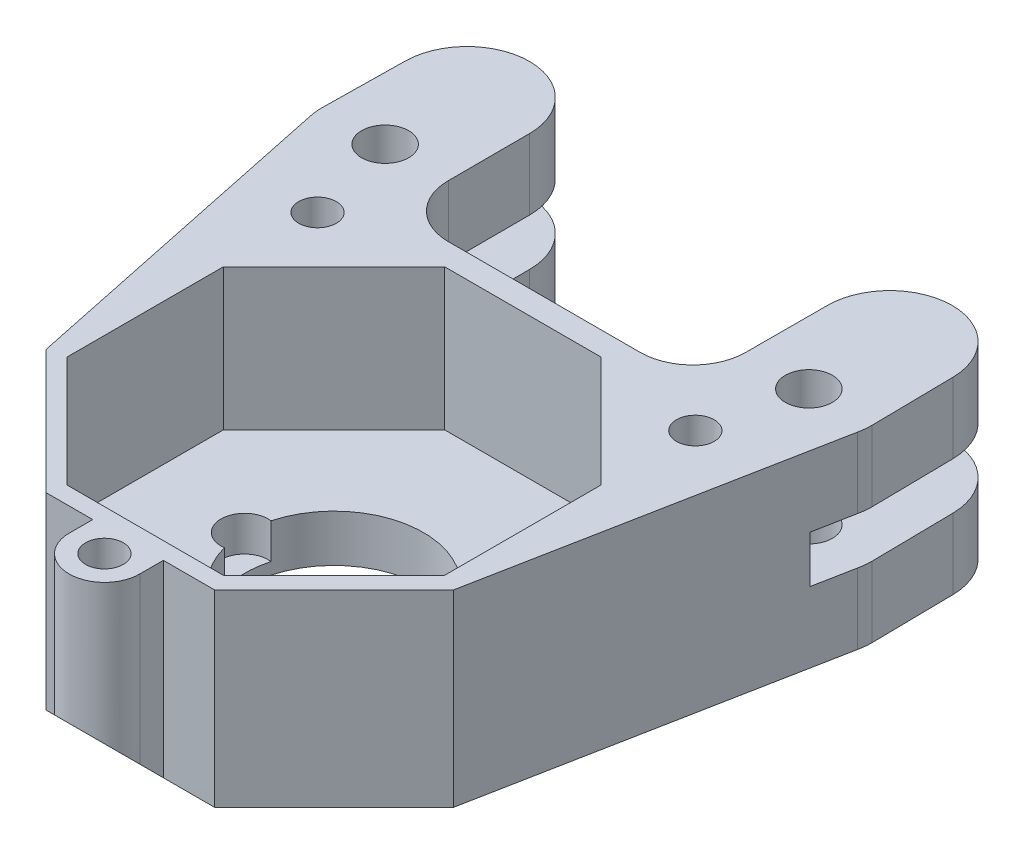
SolidWorks part; units mm, degrees
ref_plane "Front Plane" through (0, 0, 0) normal (0, 0, 1) x (1, 0, 0)
ref_plane "Top Plane" through (0, 0, 0) normal (0, 1, 0) x (1, 0, 0)
ref_plane "Right Plane" through (0, 0, 0) normal (1, 0, 0) x (0, 0, -1)
sketch "Sketch1" plane through (0, 0, 0) normal (0, 1, 0) x (1, 0, 0)
  line L0 (7.561, -35.5569) -> (17.6969, -25.421)
  line L1 (-6.7734, -35.5569) -> (7.561, -35.5569)
  line L3 (-7.1672, 0) -> (7.1672, 0)
  line L5 (-6.7734, -35.5569) -> (-17.3031, -25.0272)
  line L8 (-8.1516, 0) -> (8.1516, 0)
  line L10 (-17.3031, -25.0272) -> (-23.2516, 3.3834)
  line L12 (17.6969, -25.421) -> (23.2516, 3.3834)
  line L13 (-12.6345, 4.483) -> (-12.6501, 11.3996)
  line L14 (17.9118, 16.7228) -> (17.9119, 16.707)
  line L15 (-23.2647, 11.4761) -> (-23.3655, 4.483)
  line L16 (0, 0) -> (0, 17.0676)
  line L17 (23.2647, 11.4761) -> (23.3655, 4.483)
  line L20 (-17.9118, 16.7228) -> (-17.9119, 16.707)
  line L21 (23.2647, 11.4761) -> (23.3655, 4.483)
  line L22 (12.6345, 4.483) -> (12.6501, 11.3996)
  circle A0 centre (-18, 4.483) radius 2
  arc A1 (-23.3632, 4.6376) -> (-23.2516, 3.3834) centre (-18, 4.483) ccw
  arc A2 (23.3632, 4.6376) -> (23.2516, 3.3834) centre (18, 4.483) cw
  circle A3 centre (18, 4.483) radius 2
  arc A4 (-12.6345, 4.483) -> (-8.1516, 0) centre (-8.1516, 4.483) ccw
  arc A5 (12.6345, 4.483) -> (8.1516, 0) centre (8.1516, 4.483) cw
  arc A7 (-12.6501, 11.3996) -> (-23.2647, 11.4761) centre (-17.9577, 11.3996) ccw
  arc A8 (12.6501, 11.3996) -> (23.2647, 11.4761) centre (17.9577, 11.3996) cw
  arc A9 (12.6345, 4.483) -> (8.1516, 0) centre (8.1516, 4.483) cw
  arc A10 (23.3632, 4.6376) -> (23.2516, 3.3834) centre (18, 4.483) cw
  circle A11 centre (18, 4.483) radius 2
  circle A12 centre (0.1969, -18.0569) radius 7.6
extrude "Boss-Extrude2" add sketch "Sketch1" along normal blind 16 contours A8 L22 A5 L8 L3 A4 L13 A7 L15 A1 L10 L5 L1 L0 L12 A2 L21 L17 A12 A0 A3 region at (0.1403, 0, 10.0277)
sketch "Sketch2" plane through (0, 16, 0) normal (0, 1, 0) x (1, 0, 0)
  line L5 (-6.4512, -34.1069) -> (6.845, -34.1069)
  line L6 (-15.8531, -24.705) -> (-15.8531, -11.4088)
  line L7 (-6.4512, -2.0069) -> (6.845, -2.0069)
  line L8 (16.2469, -24.705) -> (16.2469, -11.4088)
  line L9 (6.845, -34.1069) -> (16.2469, -24.705)
  line L10 (-6.4512, -34.1069) -> (-15.8531, -24.705)
  line L11 (-15.8531, -11.4088) -> (-6.4512, -2.0069)
  line L12 (16.2469, -11.4088) -> (6.845, -2.0069)
extrude "Cut-Extrude1" cut sketch "Sketch2" against normal blind 12 contours L5 L9 L8 L12 L7 L11 L6 L10
sketch "Sketch3" plane through (0, 4, 0) normal (0, 1, 0) x (1, 0, 0)
  circle A2 centre (7.7969, -18.0569) radius 2
  circle A3 centre (0.1969, -18.0569) radius 7.6 construction
  circle A4 centre (-7.4031, -18.0569) radius 2
extrude "Cut-Extrude2" cut sketch "Sketch3" against normal blind 3
sketch "Sketch4" plane through (0, 0, 0) normal (0, 0, -1) x (-1, 0, 0)
  line L0 (0, 16) -> (0, 0)
  line L1 (8.1516, 16) -> (-8.1516, 16) construction
  line L2 (0, 8) -> (1.5061, 8)
  line L3 (1.5061, 8) -> (1.5061, 10)
  line L4 (1.5061, 8) -> (1.5061, 6)
  line L6 (-25.24, 10) -> (27.3005, 10)
  line L7 (-25.24, 10) -> (-25.24, 6)
  line L8 (-25.24, 6) -> (27.3005, 6)
  line L9 (27.3005, 10) -> (27.3005, 6)
  line M4 (8.1516, 0) -> (8.1516, 16)
  line M6 (-8.1516, 16) -> (-8.1516, 0)
extrude "Cut-Extrude3" cut sketch "Sketch4" along normal blind 34 contours L9 L6 L8 M4 | L4 L8 L6 L3 M4 | L8 L0 L6 M6 | L6 L0 L2 L3 | L0 L8 L4 L2 | L7 L8 L6 M6 region at (-0.7531, 9, 0) region at (4.0758, 8, 0) region at (-0.7531, 7, 0) region at (16.6958, 8, 0) region at (-4.8288, 8, 0) region at (-17.726, 8, 0)
sketch "Sketch5" plane through (0, 16, 0) normal (0, 1, 0) x (1, 0, 0)
  line L0 (16.2469, -11.4088) -> (16.2469, -3.4088)
  line L1 (-15.8531, -11.4088) -> (-15.8531, -3.4088)
  circle A0 centre (16.2469, -3.4088) radius 1.6
  circle A1 centre (-15.8531, -3.4088) radius 1.6
extrude "Cut-Extrude4" cut sketch "Sketch5" against normal blind 8 contours A0 | A1 region at (17.3463, 16, 4.5081) region at (-14.7537, 16, 4.5081)
sketch "Sketch6" plane through (0, 16, 0) normal (0, 1, 0) x (1, 0, 0)
  line L0 (0.1969, -34.1069) -> (0.1969, -37.5616)
  line L1 (-6.4512, -34.1069) -> (6.845, -34.1069) construction
  line L6 (3.1969, -35.5569) -> (-2.8031, -35.5569)
  line L7 (3.1969, -37.5616) -> (3.1969, -35.5569)
  line L8 (-2.8031, -37.5616) -> (-2.8031, -35.5569)
  arc A2 (3.1969, -37.5616) -> (-2.8031, -37.5616) centre (0.1969, -37.5616) cw
  circle A3 centre (0.1969, -37.5616) radius 1.6
  line M19 (-6.7734, -35.5569) -> (7.561, -35.5569)
extrude "Boss-Extrude4" add sketch "Sketch6" against normal blind 7 contours A3 L8 A2 L7 M19 region at (1.6969, 16, 35.635)
sketch "Sketch8" plane through (0, 16, 0) normal (0, 1, 0) x (1, 0, 0)
  line L0 (3.1969, -37.5616) -> (3.1969, -35.5569)
  line L1 (3.1969, -35.5569) -> (7.561, -35.5569)
  line L2 (7.561, -35.5569) -> (17.6969, -25.421)
  line L3 (17.6969, -25.421) -> (19.6421, -3.713)
  line L10 (-17.3031, -25.421) -> (-19.2483, -3.713)
  line L11 (-7.1672, -35.5569) -> (-17.3031, -25.421)
  line L12 (-2.8031, -35.5569) -> (-7.1672, -35.5569)
  line L13 (-2.8031, -37.5616) -> (-2.8031, -35.5569)
  line L14 (16.2469, 0) -> (-15.8531, 0)
  circle A0 centre (0.1969, -37.5616) radius 1.6
  arc A1 (-2.8031, -37.5616) -> (3.1969, -37.5616) centre (0.1969, -37.5616) ccw
  circle A2 centre (16.2469, -3.4088) radius 1.6
  circle A3 centre (-15.8531, -3.4088) radius 1.6
  arc A5 (19.6421, -3.713) -> (16.2469, 0) centre (16.2469, -3.4088) ccw
  arc A6 (-19.2483, -3.713) -> (-15.8531, 0) centre (-15.8531, -3.4088) cw
  circle A7 centre (-15.8531, -3.4088) radius 1.6
sketch "Sketch9" plane through (0, 9, 0) normal (0, -1, 0) x (1, 0, 0)
  circle A0 centre (0.1969, 37.5616) radius 1.6
extrude "Boss-Extrude7" add sketch "Sketch9" against normal blind 1
chamfer "Chamfer2" distance 9 angle 45 1 edges at (0.1969, 9, 35.5569)
